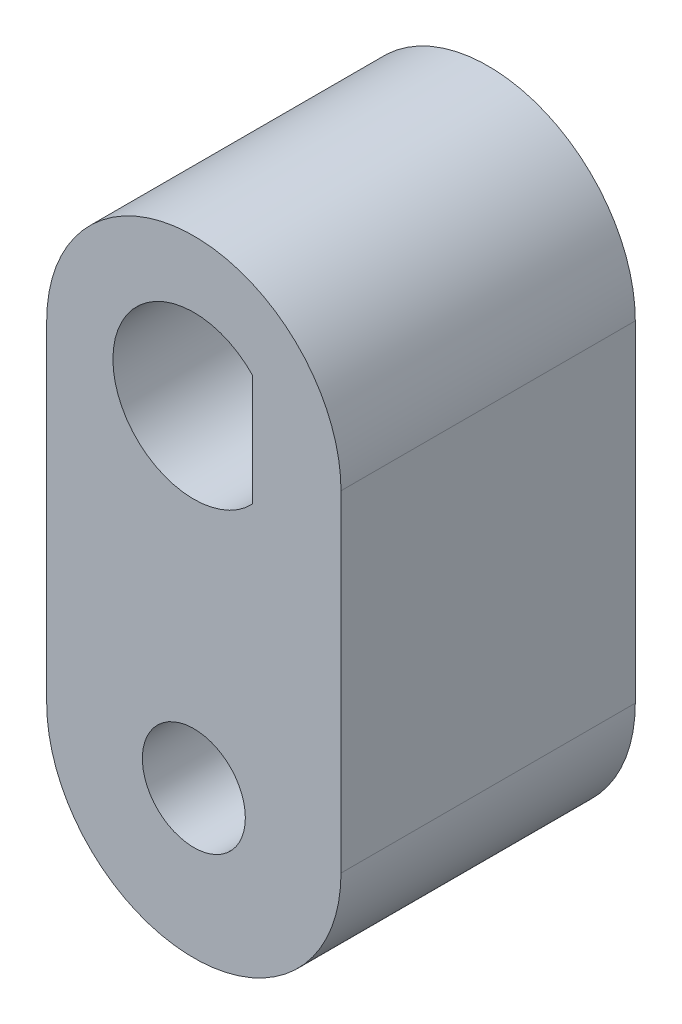
SolidWorks part; units mm, degrees
ref_plane "前视基准面" through (0, 0, 0) normal (0, 0, 1) x (1, 0, 0)
ref_plane "上视基准面" through (0, 0, 0) normal (0, 1, 0) x (1, 0, 0)
ref_plane "右视基准面" through (0, 0, 0) normal (1, 0, 0) x (0, 0, -1)
sketch "草图1" plane through (0, 0, 0) normal (0, 0, 1) x (1, 0, 0)
  line L0 (1.6, 1.51) -> (1.6, -1.51)
  line L12 (3.3486, -9) -> (1.6743, -6.1)
  line L13 (1.6743, -6.1) -> (-1.6743, -6.1)
  line L14 (-1.6743, -6.1) -> (-3.3486, -9)
  line L15 (-3.3486, -9) -> (-1.6743, -11.9)
  line L16 (-1.6743, -11.9) -> (1.6743, -11.9)
  line L17 (1.6743, -11.9) -> (3.3486, -9)
  line L20 (0, 0) -> (0, -9) construction
  line L21 (4, 0) -> (4, -9)
  line L22 (-4, 0) -> (-4, -9)
  circle A1 centre (0, 0) radius 2.2
  circle A16 centre (0, -9) radius 1.4
  circle A18 centre (0, -9) radius 2.9 construction
  arc A21 (4, 0) -> (-4, 0) centre (0, 0) ccw
  arc A22 (-4, -9) -> (4, -9) centre (0, -9) ccw
  circle A24 centre (0, -9) radius 2.4
  point P24 (0, 0)
  point P29 (0, -4.5)
  dimension "D1" = 4.4
  dimension "D5" = 9
  dimension "D2" = 1.6
extrude "凸台-拉伸2" add sketch "草图1" along normal blind 8 contours L22 A22 L21 A21
extrude "切除-拉伸2" cut sketch "草图1<6>" along normal blind 8 contours L0 A1 | A16 region at (-0.1644, 0, 0)
sketch "草图1<6>" plane through (0, 0, 0) normal (0, 0, 1) x (1, 0, 0) same geometry as "草图1"
